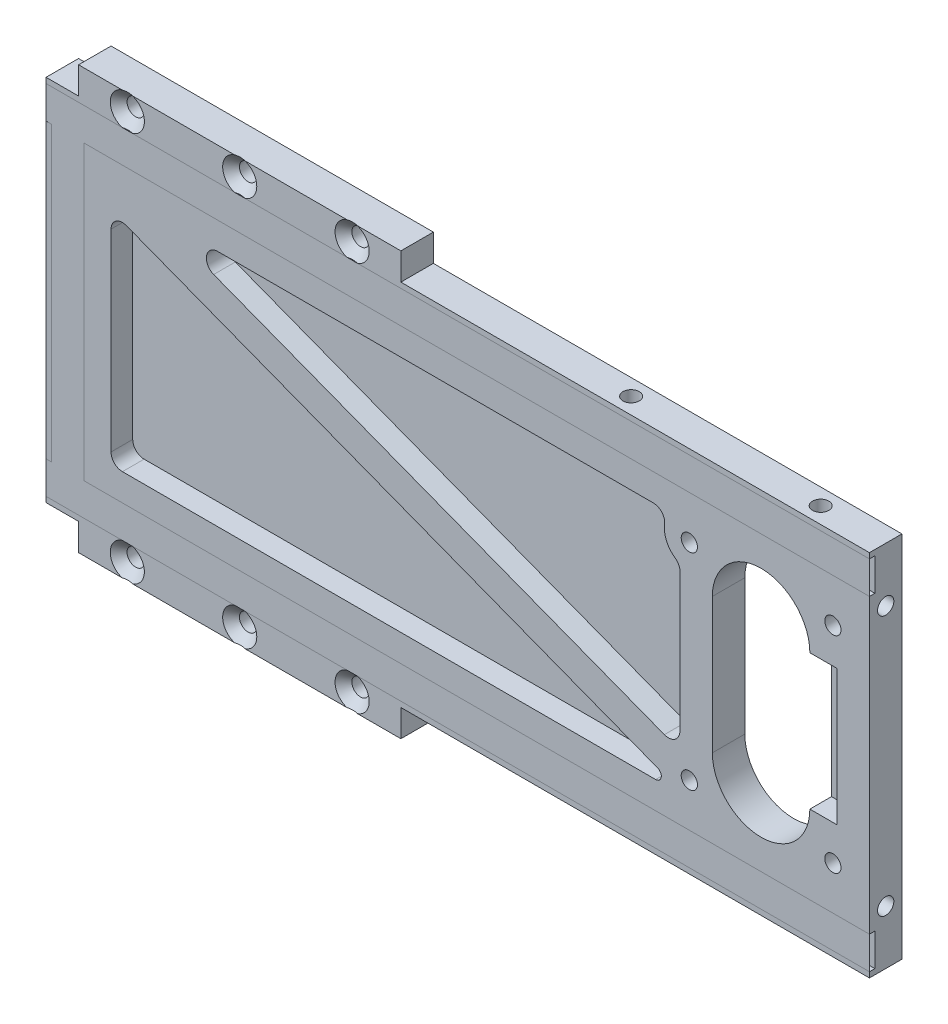
SolidWorks part; units mm, degrees
note: The reader was unsure of these and kept them because the rebuilt part matched: shared geometry of "ｽｹｯﾁ1<5>", "ｽｹｯﾁ1<3>", "ｽｹｯﾁ1<7>", "ｽｹｯﾁ1<8>".
material "3.1325 (EN-AW 2017A)"
ref_plane "正面" through (0, 0, 0) normal (0, 0, 1) x (1, 0, 0)
ref_plane "平面" through (0, 0, 0) normal (0, 1, 0) x (1, 0, 0)
ref_plane "右側面" through (0, 0, 0) normal (1, 0, 0) x (0, 0, -1)
sketch "ｽｹｯﾁ1" plane through (0, 0, 0) normal (0, 0, 1) x (1, 0, 0)
  line L0 (0, 0) -> (38483.9915, 0) construction
  line L1 (-76, 30) -> (76, 30) construction
  line L2 (-76, 34) -> (76, 34)
  line L3 (-76, 34) -> (-76, -34)
  line L4 (-76, -34) -> (76, -34)
  line L5 (76, 34) -> (76, -34)
  line L6 (-76, 33) -> (76, 33)
  line L7 (-76, 27) -> (-75, 27)
  line L8 (-75, 27) -> (-75, -27)
  line L9 (-69, -27) -> (-69, 27)
  line L10 (-69, 27) -> (76, 27)
  line L11 (-72, 34) -> (-72, -34) construction
  line L12 (0, 0) -> (0, -50000) construction
  line L13 (-76, -33) -> (76, -33)
  line L14 (-76, -27) -> (-75, -27)
  line L15 (-69, -27) -> (76, -27)
  line L16 (-70, 34) -> (-70, 39)
  line L17 (-70, 39) -> (-10.5, 39)
  line L18 (-10.5, 39) -> (-10.5, 34)
  line L19 (-70, -34) -> (-70, -39)
  line L20 (-10.5, -39) -> (-10.5, -34)
  line L21 (-70, -39) -> (-10.5, -39)
  line L22 (47, 12.5) -> (47, -12.5)
  line L23 (-40.25, 39) -> (-40.25, 33) construction
  line L24 (65, -12.5) -> (65, 12.5)
  line L26 (56, 19) -> (56, -19) construction
  line L27 (65, 12.5) -> (70, 12.5)
  line L28 (70, 12.5) -> (70, -12.5)
  line L29 (70, -12.5) -> (65, -12.5)
  arc A0 (47, 12.5) -> (65, 12.5) centre (56, 12.5) cw
  arc A1 (47, -12.5) -> (65, -12.5) centre (56, -12.5) ccw
  point P19 (-66, 30)
  point P34 (-66, -30)
  point P35 (-72, 19)
  point P44 (-61, 36)
  point P45 (-40.25, 39)
  point P46 (-40.25, 36)
  point P47 (-19.5, 36)
  point P49 (-19.5, -36)
  point P50 (-40.25, -36)
  point P51 (-61, -36)
  point P56 (56, 19)
  point P59 (42.75, 19)
  point P61 (69.25, 19)
  point P62 (69.25, -19)
  point P65 (42.75, -19)
  point P66 (29, 0)
  point P67 (64, 0)
  point P68 (-72, 12)
  point P70 (-72, -12)
  point P71 (-72, -19)
  point P73 (56, 0)
  point P76 (0, 24)
  point P77 (0, -24)
  point P80 (-40.25, 36)
  dimension "D16" = 25
  dimension "D1" = 6
  dimension "D2" = 1
  dimension "D3" = 1
  dimension "D4" = 6
  dimension "D5" = 54
  dimension "D6" = 152
  dimension "D8" = 10
  dimension "D10" = 24
  dimension "D11" = 6
  dimension "D12" = 59.5
  dimension "D13" = 5
  dimension "D15" = 41.5
  dimension "D17" = 18
  dimension "D18" = 3
  dimension "D19" = 26.5
  dimension "D20" = 11
  dimension "D21" = 6
  dimension "D22" = 38
  dimension "D23" = 38
  dimension "D24" = 35
  dimension "D25" = 12
  dimension "D26" = 48
  dimension "D14" = 3
extrude "ﾎﾞｽ - 押し出し1" add sketch "ｽｹｯﾁ1" against normal mid plane 6 contours L2 L5 L4 L3
extrude "ﾎﾞｽ - 押し出し2" add sketch "ｽｹｯﾁ1<5>" along normal up to surface and the other way up to surface contours L18 L17 L16 L2 | L19 L21 L20 L4 up to face at (0, 0, 3) other way up to face at (0, 0, -3)
sketch "ｽｹｯﾁ1<5>" plane through (0, 0, 0) normal (0, 0, 1) x (1, 0, 0) same geometry as "ｽｹｯﾁ1"
extrude "ｶｯﾄ - 押し出し1" cut sketch "ｽｹｯﾁ1<3>" against normal blind 1 from surface contours L15 L9 L10 L5 L6 L3 L7 L8 L14 L13 starting at face at (-34.5417, 0, 3)
sketch "ｽｹｯﾁ1<3>" plane through (0, 0, 0) normal (0, 0, 1) x (1, 0, 0) same geometry as "ｽｹｯﾁ1"
extrude "ｶｯﾄ - 押し出し2" cut sketch "ｽｹｯﾁ1<7>" against normal through all both and the other way through all
sketch "ｽｹｯﾁ1<7>" plane through (0, 0, 0) normal (0, 0, 1) x (1, 0, 0) same geometry as "ｽｹｯﾁ1"
extrude "ｶｯﾄ - 押し出し3" cut sketch "ｽｹｯﾁ1<8>" against normal blind 1 and the other way through all contours L29 L28 L27 L24
sketch "ｽｹｯﾁ1<8>" plane through (0, 0, 0) normal (0, 0, 1) x (1, 0, 0) same geometry as "ｽｹｯﾁ1"
hole_wizard "M3 丸皿ねじ用皿穴3" positions "3Dｽｹｯﾁ2" profile "ｽｹｯﾁ2" countersink size "M3" standard "JIS" end condition through all
sketch3d "3Dｽｹｯﾁ2"
  point P8 (-66, 30, -3)
  point P15 (-66, -30, -3)
  point P17 (-66, -30, -3)
sketch "ｽｹｯﾁ2" plane through (-66, 30, -3) normal (1, 0, 0) x (0, 1, 0)
  line L0 (0, 0) -> (0, 6.0001)
  line L1 (0, 6.0001) -> (1.6, 6.0001)
  line L2 (1.6, 6.0001) -> (1.6, 1.55)
  line L3 (1.6, 1.55) -> (3.15, 0)
  line L5 (3.15, 0) -> (0, 0)
  line L6 (-1.6, 1.55) -> (-3.15, 0) construction
  line L11 (0, -6.35) -> (0, 107.95) construction
  dimension "通し穴の直径" = 3.2
  dimension "通し穴の深さ" = 6.0001
  dimension "表面の皿穴の直径" = 6.3
  dimension "表面の皿穴の角度" = 90
pattern_linear "直線ﾊﾟﾀｰﾝ1" count 6 spacing 25 along (1, 0, 0) of "M3 丸皿ねじ用皿穴3"
hole_wizard "M3 丸皿ねじ用皿穴2" positions "3Dｽｹｯﾁ6" profile "ｽｹｯﾁ7" countersink size "M3" standard "JIS" end condition through all
sketch3d "3Dｽｹｯﾁ6"
  point P0 (-61, 36, 3)
  point P2 (-40.25, 36, 3)
  point P4 (-19.5, 36, 3)
  point P6 (-61, -36, 3)
  point P8 (-40.25, -36, 3)
  point P10 (-19.5, -36, 3)
sketch "ｽｹｯﾁ7" plane through (-61, 36, 3) normal (1, 0, 0) x (0, -1, 0)
  line L0 (0, 0) -> (0, 6.0001)
  line L1 (0, 6.0001) -> (1.6, 6.0001)
  line L2 (1.6, 6.0001) -> (1.6, 1.55)
  line L3 (1.6, 1.55) -> (3.15, 0)
  line L5 (3.15, 0) -> (0, 0)
  line L6 (-1.6, 1.55) -> (-3.15, 0) construction
  line L11 (0, -6.35) -> (0, 107.95) construction
  dimension "通し穴の直径" = 3.2
  dimension "通し穴の深さ" = 6.0001
  dimension "表面の皿穴の直径" = 6.3
  dimension "表面の皿穴の角度" = 90
hole_wizard "M3 丸皿ねじ用皿穴1" positions "3Dｽｹｯﾁ7" profile "ｽｹｯﾁ8" countersink size "M3" standard "JIS"
sketch3d "3Dｽｹｯﾁ7"
  point P0 (-72, 19, -3)
  point P4 (-72, -19, -3)
sketch "ｽｹｯﾁ8" plane through (-72, 19, -3) normal (1, 0, 0) x (0, 1, 0)
  line L0 (0, 0) -> (0, 6.9614)
  line L1 (0, 6.9614) -> (1.6, 6)
  line L2 (1.6, 6) -> (1.6, 1.55)
  line L3 (1.6, 1.55) -> (3.15, 0)
  line L5 (3.15, 0) -> (0, 0)
  line L6 (-1.6, 1.55) -> (-3.15, 0) construction
  line L10 (0, 6.9614) -> (-1.6, 6) construction
  line L11 (0, -6.35) -> (0, 107.95) construction
  dimension "穴の直径" = 3.2
  dimension "穴の深さ" = 6
  dimension "表面の皿穴の直径" = 6.3
  dimension "表面の皿穴の角度" = 90
  dimension "ﾄﾞﾘﾙ角度" = 118
hole_wizard "M3x0.5 ねじ穴3" positions "3Dｽｹｯﾁ3" profile "ｽｹｯﾁ4" tap size "M3x0.5" standard "JIS"
sketch3d "3Dｽｹｯﾁ3"
  point P8 (76, 24, 0)
  point P12 (76, -24, 0)
sketch "ｽｹｯﾁ4" plane through (76, 24, 0) normal (0, 1, 0) x (0, 0, -1)
  line L0 (0, 0) -> (0, 9.2511)
  line L1 (0, 9.2511) -> (1.25, 8.5)
  line L2 (1.25, 8.5) -> (1.25, 6)
  line L3 (1.25, 6) -> (1.5, 6)
  line L4 (1.5, 6) -> (1.5, 0)
  line L5 (1.5, 0) -> (0, 0)
  line L10 (0, 9.2511) -> (-1.25, 8.5) construction
  line L11 (0, -6.35) -> (0, 107.95) construction
  dimension "ねじ下穴ﾄﾞﾘﾙ直径" = 2.5
  dimension "ねじ下穴ﾄﾞﾘﾙの深さ" = 8.5
  dimension "ねじ山の主要直径" = 3
  dimension "ねじ山の深さ" = 6
  dimension "ﾄﾞﾘﾙ角度" = 118
hole_wizard "M3x0.5 ねじ穴4" positions "3Dｽｹｯﾁ5" profile "ｽｹｯﾁ6" tap size "M3x0.5" standard "JIS" end condition through all
sketch3d "3Dｽｹｯﾁ5"
  point P0 (42.75, 19, 3)
  point P4 (69.25, 19, 3)
  point P6 (69.25, -19, 3)
  point P10 (42.75, -19, 3)
sketch "ｽｹｯﾁ6" plane through (42.75, 19, 3) normal (1, 0, 0) x (0, -1, 0)
  line L0 (0, 0) -> (0, 6.0001)
  line L1 (0, 6.0001) -> (1.5, 6.0001)
  line L2 (1.5, 6.0001) -> (1.5, 0)
  line L5 (1.5, 0) -> (0, 0)
  line L11 (0, -6.35) -> (0, 107.95) construction
  dimension "ねじ山の主要直径" = 3
  dimension "次ｻｰﾌｪｽまでのねじ下穴ﾄﾞﾘﾙの深さ" = 6.0001
hole_wizard "M3x0.5 ねじ穴5" positions "3Dｽｹｯﾁ8" profile "ｽｹｯﾁ10" tap size "M3x0.5" standard "JIS"
sketch3d "3Dｽｹｯﾁ8"
  point P0 (29, -34, 0)
  point P2 (64, -34, 0)
  point P8 (-76, -12, 0)
sketch "ｽｹｯﾁ10" plane through (29, -34, 0) normal (1, 0, 0) x (0, 0, -1)
  line L0 (0, 0) -> (0, 9.2511)
  line L1 (0, 9.2511) -> (1.25, 8.5)
  line L2 (1.25, 8.5) -> (1.25, 6)
  line L3 (1.25, 6) -> (1.5, 6)
  line L4 (1.5, 6) -> (1.5, 0)
  line L5 (1.5, 0) -> (0, 0)
  line L10 (0, 9.2511) -> (-1.25, 8.5) construction
  line L11 (0, -6.35) -> (0, 107.95) construction
  dimension "ねじ下穴ﾄﾞﾘﾙ直径" = 2.5
  dimension "ねじ下穴ﾄﾞﾘﾙの深さ" = 8.5
  dimension "ねじ山の主要直径" = 3
  dimension "ねじ山の深さ" = 6
  dimension "ﾄﾞﾘﾙ角度" = 118
hole_wizard "M3x0.5 ねじ穴2" positions "3Dｽｹｯﾁ9" profile "ｽｹｯﾁ11" tap size "M3x0.5" standard "JIS"
sketch3d "3Dｽｹｯﾁ9"
  point P0 (29, 34, 0)
  point P2 (64, 34, 0)
  point P7 (-76, 12, 0)
sketch "ｽｹｯﾁ11" plane through (29, 34, 0) normal (1, 0, 0) x (0, 0, 1)
  line L0 (0, 0) -> (0, 9.2511)
  line L1 (0, 9.2511) -> (1.25, 8.5)
  line L2 (1.25, 8.5) -> (1.25, 6)
  line L3 (1.25, 6) -> (1.5, 6)
  line L4 (1.5, 6) -> (1.5, 0)
  line L5 (1.5, 0) -> (0, 0)
  line L10 (0, 9.2511) -> (-1.25, 8.5) construction
  line L11 (0, -6.35) -> (0, 107.95) construction
  dimension "ねじ下穴ﾄﾞﾘﾙ直径" = 2.5
  dimension "ねじ下穴ﾄﾞﾘﾙの深さ" = 8.5
  dimension "ねじ山の主要直径" = 3
  dimension "ねじ山の深さ" = 6
  dimension "ﾄﾞﾘﾙ角度" = 118
sketch "ｽｹｯﾁ12" [suppressed] plane through (0, 0, 3) normal (0, 0, 1) x (1, 0, 0)
  line L12 (70, -21) -> (-63, 21) construction
  line L13 (70, -17.854) -> (-53.0376, 21)
  line L14 (60.0376, -21) -> (-63, 17.854)
  line L15 (70.9034, -18.1393) -> (-62.0966, 23.8607) construction
  line L16 (70, -21) -> (70, 21)
  line L17 (70, 21) -> (-63, 21)
  line L18 (-63, 21) -> (-63, -21)
  line L19 (-63, -21) -> (70, -21)
  line L20 (70, -17.854) -> (70, 21)
  line L21 (70, 21) -> (-53.0376, 21)
  line L22 (-63, 17.854) -> (-63, -21)
  line L23 (-63, -21) -> (60.0376, -21)
  line L24 (69.0966, -23.8607) -> (-63.9034, 18.1393) construction
  dimension "D2" = 3
  dimension "D1" = 6
  dimension "D3" = 3
extrude "ｶｯﾄ - 押し出し5" [suppressed] cut sketch "ｽｹｯﾁ12" against normal blind 4
fillet "ﾌｨﾚｯﾄ2" [suppressed] radius 2.1
sketch "ｽｹｯﾁ13" plane through (0, 0, 3) normal (0, 0, 1) x (1, 0, 0)
  line L7 (0, 0) -> (85.6999, 0) construction
  line L8 (71, -22) -> (71, 22)
  line L9 (71, 22) -> (-64, 22)
  line L10 (-64, 22) -> (-64, -22)
  line L11 (-64, -22) -> (71, -22)
  line L13 (39.2609, 22) -> (-55.6327, 22)
  line L14 (-64, 18.7863) -> (-64, -22)
  line L15 (-64, -22) -> (36.5313, -22)
  line L16 (41, 12.5) -> (41, -12.5)
  line L17 (41, 12.5) -> (41, -12.5)
  line L18 (-64, 18.7863) -> (36.9078, -19.9698)
  line L19 (-64, 22) -> (42.75, -19) construction
  line L20 (-55.6327, 22) -> (41.2466, -15.2089)
  line L21 (-62.9244, 24.8005) -> (43.8256, -16.1995) construction
  line L22 (-65.0756, 19.1995) -> (41.6744, -21.8005) construction
  arc A0 (39.2609, 22) -> (41.1596, 14.6821) centre (42.75, 19) ccw
  arc A5 (41.1596, 14.6821) -> (41, 12.5) centre (56, 12.5) ccw
  arc A6 (41, -12.5) -> (71, -12.5) centre (56, -12.5) ccw
  arc A7 (71, 12.5) -> (41, 12.5) centre (56, 12.5) ccw
  arc A8 (41, -12.5) -> (41.2466, -15.2089) centre (56, -12.5) ccw
  arc A9 (36.5313, -22) -> (36.9078, -19.9698) centre (36.5313, -20.95) ccw
  dimension "D2" = 9.203
  dimension "D6" = 2.1
  dimension "D4" = 3
  dimension "D1" = 5
  dimension "D3" = 6
  dimension "D5" = 3
extrude "ｶｯﾄ - 押し出し6" cut sketch "ｽｹｯﾁ13" against normal blind 4
fillet "ﾌｨﾚｯﾄ3" radius 2.1 6 edges at (-64, -22, 1) (-64, 18.7863, 1) (39.2609, 22, 1) (-55.6327, 22, 1) (41.1596, 14.6821, 1) (41.2466, -15.2089, 1)
sketch "ｽｹｯﾁ14" plane through (0, 0, 2) normal (0, 0, 1) x (1, 0, 0)
  line L0 (77.05, -28.05) -> (77.05, -31.95)
  line L1 (20.0928, 0) -> (0, 0) construction
  line L2 (0, 0) -> (0, -11.2314) construction
  line L3 (-77.05, -28.05) -> (-77.05, -31.95)
  line L4 (77.05, 28.05) -> (77.05, 31.95)
  line L5 (-77.05, 28.05) -> (-77.05, 31.95)
  line L12 (76, -33) -> (76, -27) construction
  line L24 (-75, 27) -> (-75, -27)
  line L25 (-75, -27) -> (-76, -27)
  line L26 (-76, -27) -> (-76, -33)
  line L27 (-76, -33) -> (76, -33)
  line L28 (76, -33) -> (76, -27)
  line L29 (76, -27) -> (-69, -27)
  line L30 (-69, -27) -> (-69, 27)
  line L31 (-69, 27) -> (76, 27)
  line L32 (76, 27) -> (76, 33)
  line L33 (76, 33) -> (-76, 33)
  line L34 (-76, 33) -> (-76, 27)
  line L35 (-76, 27) -> (-75, 27)
  line L36 (-75, 27) -> (-75, -27)
  line L37 (-75, -27) -> (-76, -27)
  line L39 (-76, -33) -> (76, -33)
  line L41 (76, -27) -> (-69, -27)
  line L42 (-69, -27) -> (-69, 27)
  line L43 (-69, 27) -> (76, 27)
  line L45 (76, 33) -> (-76, 33)
  line L47 (-76, 27) -> (-75, 27)
  arc A0 (77.05, -28.05) -> (76, -27) centre (76, -28.05) ccw
  arc A1 (76, -33) -> (77.05, -31.95) centre (76, -31.95) ccw
  arc A2 (-76, -33) -> (-77.05, -31.95) centre (-76, -31.95) cw
  arc A3 (-77.05, -28.05) -> (-76, -27) centre (-76, -28.05) cw
  arc A4 (76, 33) -> (77.05, 31.95) centre (76, 31.95) cw
  arc A5 (77.05, 28.05) -> (76, 27) centre (76, 28.05) cw
  arc A6 (-76, 33) -> (-77.05, 31.95) centre (-76, 31.95) ccw
  arc A7 (-77.05, 28.05) -> (-76, 27) centre (-76, 28.05) ccw
  dimension "D2" = 2.1
  dimension "D1" = 0
sketch "ｽｹｯﾁ15" plane through (0, 0, 3) normal (0, 0, 1) x (1, 0, 0)
  line L4 (68.5151, 12.5) -> (65, 12.5)
  line L5 (70, -11.0151) -> (70, 11.0151)
  line L6 (65, -12.5) -> (68.5151, -12.5)
  line L7 (63.95, 11.45) -> (63.95, -11.45)
  arc A4 (65, 12.5) -> (63.95, 11.45) centre (65, 11.45) ccw
  arc A5 (70, 11.0151) -> (68.5151, 12.5) centre (69.2575, 11.7575) ccw
  arc A6 (68.5151, -12.5) -> (70, -11.0151) centre (69.2575, -11.7575) ccw
  arc A7 (63.95, -11.45) -> (65, -12.5) centre (65, -11.45) ccw
sketch "ｽｹｯﾁ17" plane through (0, 0, 3) normal (0, 0, 1) x (1, 0, 0)
  line L12 (-75, 27) -> (-75, -27)
  line L13 (-75, -27) -> (-76, -27)
  line L14 (-76, -27) -> (-76, -33)
  line L15 (-76, -33) -> (76, -33)
  line L16 (76, -33) -> (76, -27)
  line L17 (76, -27) -> (-69, -27)
  line L18 (-69, -27) -> (-69, 27)
  line L19 (-69, 27) -> (76, 27)
  line L20 (76, 27) -> (76, 33)
  line L21 (76, 33) -> (-76, 33)
  line L22 (-76, 33) -> (-76, 27)
  line L23 (-76, 27) -> (-75, 27)
  line L24 (-75, 27) -> (-75, -27)
  line L25 (-75, -27) -> (-76, -27)
  line L26 (-76, -27) -> (-76, -33)
  line L27 (-76, -33) -> (76, -33)
  line L28 (76, -33) -> (76, -27)
  line L29 (76, -27) -> (-69, -27)
  line L30 (-69, -27) -> (-69, 27)
  line L31 (-69, 27) -> (76, 27)
  line L32 (76, 27) -> (76, 33)
  line L33 (76, 33) -> (-76, 33)
  line L34 (-76, 33) -> (-76, 27)
  line L35 (-76, 27) -> (-75, 27)
  dimension "D1" = 0
surface "グリス" sketch "ｽｹｯﾁ17"
equation "\"回路ボックス横幅\" = 316"
equation "\"回路ボックス板厚\"= 6"
equation "\"接合溝\"= 1"
equation "\"ミル径\"= 1"
equation "\"板接合ねじ間隔\"=30"
equation "\"フリッパ駆動ユニット+床板取付け位置\"= 16"
equation "\"タップ下穴深さ板接合部\"= \"タップ深さ板接合部\" + \"タップ食いつき部長さ\""
equation "\"タップ食いつき部長さ\"= 2"
equation "\"タップ深さ板接合部\"= 3"
